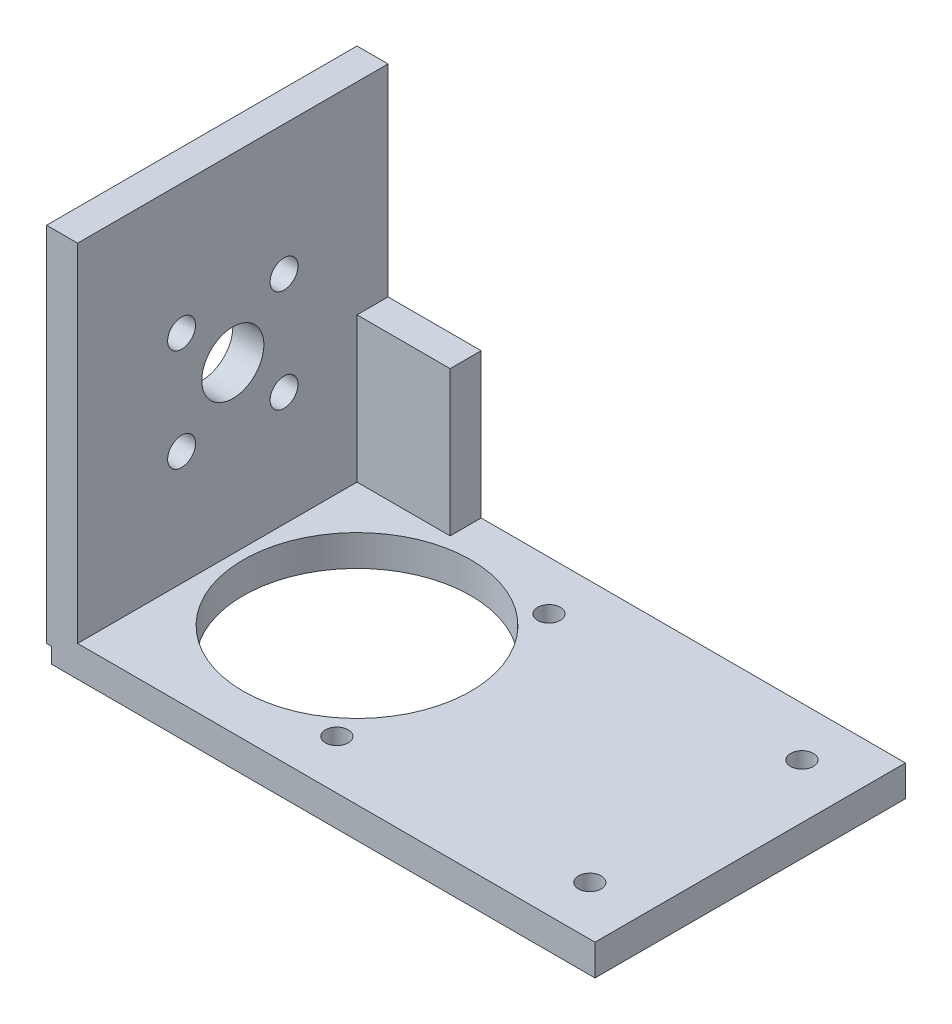
SolidWorks part; units mm, degrees
ref_plane "Front Plane" through (0, 0, 0) normal (0, 0, 1) x (1, 0, 0)
ref_plane "Top Plane" through (0, 0, 0) normal (0, 1, 0) x (1, 0, 0)
ref_plane "Right Plane" through (0, 0, 0) normal (1, 0, 0) x (0, 0, -1)
ref_plane "PZ_m15_000" through (0, 0, -15) normal (0, 0, 1) x (1, 0, 0)
sketch "S_box1" plane through (0, 0, -15) normal (0, 0, 1) x (1, 0, 0)
  line L0 (-15, -17.5) -> (-12, -17.5)
  line L1 (-12, -17.5) -> (-12, 17.5)
  line L2 (-12, 17.5) -> (-15, 17.5)
  line L3 (-15, 17.5) -> (-15, -17.5)
  dimension "P1" = 15
  dimension "P2" = 17.5
  dimension "P3" = 12
  dimension "P4" = 17.5
  dimension "P5" = 12
  dimension "P6" = 17.5
  dimension "P7" = 15
  dimension "P8" = 17.5
extrude "Boss_1" add sketch "S_box1" along normal blind 30
sketch "S_box2" plane through (0, 0, -15) normal (0, 0, 1) x (1, 0, 0)
  line L0 (-14.5, -19) -> (38, -19)
  line L1 (38, -19) -> (38, -16)
  line L2 (38, -16) -> (-14.5, -16)
  line L3 (-14.5, -16) -> (-14.5, -19)
  dimension "P1" = 14.5
  dimension "P2" = 19
  dimension "P3" = 38
  dimension "P4" = 19
  dimension "P5" = 38
  dimension "P6" = 16
  dimension "P7" = 14.5
  dimension "P8" = 16
extrude "Boss_2" add sketch "S_box2" along normal blind 30
sketch "S_box3" plane through (0, 0, -15) normal (0, 0, 1) x (1, 0, 0)
  line L0 (-14.5, -18.5) -> (-3, -18.5)
  line L1 (-3, -18.5) -> (-3, -2)
  line L2 (-3, -2) -> (-14.5, -2)
  line L3 (-14.5, -2) -> (-14.5, -18.5)
  dimension "P1" = 14.5
  dimension "P2" = 18.5
  dimension "P3" = 3
  dimension "P4" = 18.5
  dimension "P5" = 3
  dimension "P6" = 2
  dimension "P7" = 14.5
  dimension "P8" = 2
extrude "Boss_3" add sketch "S_box3" along normal blind 3
ref_plane "PX_m15_100" through (-15.1, 0, 0) normal (1, 0, 0) x (0, 0, -1)
sketch "S_hole4" plane through (-15.1, 0, 0) normal (1, 0, 0) x (0, 0, -1)
  circle A0 centre (0, 0) radius 3
  dimension "D1_S_hole4" = 6
extrude "Hole_4" cut sketch "S_hole4" along normal blind 3.2
sketch "S_hole5" plane through (-15.1, 0, 0) normal (1, 0, 0) x (0, 0, -1)
  circle A0 centre (-4.9497, 4.9497) radius 1.35
  dimension "D1_S_hole5" = 2.7
  dimension "P2" = 4.9497
  dimension "P3" = 4.9497
extrude "Hole_5" cut sketch "S_hole5" along normal blind 3.2
sketch "S_hole6" plane through (-15.1, 0, 0) normal (1, 0, 0) x (0, 0, -1)
  circle A0 centre (-4.9497, -4.9497) radius 1.35
  dimension "D1_S_hole6" = 2.7
  dimension "P2" = 4.9497
  dimension "P3" = 4.9497
extrude "Hole_6" cut sketch "S_hole6" along normal blind 3.2
sketch "S_hole7" plane through (-15.1, 0, 0) normal (1, 0, 0) x (0, 0, -1)
  circle A0 centre (4.9497, -4.9497) radius 1.35
  dimension "D1_S_hole7" = 2.7
  dimension "P2" = 4.9497
  dimension "P3" = 4.9497
extrude "Hole_7" cut sketch "S_hole7" along normal blind 3.2
sketch "S_hole8" plane through (-15.1, 0, 0) normal (1, 0, 0) x (0, 0, -1)
  circle A0 centre (4.9497, 4.9497) radius 1.35
  dimension "D1_S_hole8" = 2.7
  dimension "P2" = 4.9497
  dimension "P3" = 4.9497
extrude "Hole_8" cut sketch "S_hole8" along normal blind 3.2
ref_plane "PY_m19_100" through (0, -19.1, 0) normal (0, 1, 0) x (1, 0, 0)
sketch "S_hole9" plane through (0, -19.1, 0) normal (0, 1, 0) x (1, 0, 0)
  circle A0 centre (0, 0) radius 11
  dimension "D1_S_hole9" = 22
extrude "Hole_9" cut sketch "S_hole9" along normal blind 3.2
sketch "S_hole10" plane through (0, -19.1, 0) normal (0, 1, 0) x (1, 0, 0)
  circle A0 centre (8.3, 10.25) radius 1.1
  dimension "D1_S_hole10" = 2.2
  dimension "P2" = 8.3
  dimension "P3" = 10.25
extrude "Hole_10" cut sketch "S_hole10" along normal blind 3.2
sketch "S_hole11" plane through (0, -19.1, 0) normal (0, 1, 0) x (1, 0, 0)
  circle A0 centre (8.3, -10.25) radius 1.1
  dimension "D1_S_hole11" = 2.2
  dimension "P2" = 8.3
  dimension "P3" = 10.25
extrude "Hole_11" cut sketch "S_hole11" along normal blind 3.2
sketch "S_hole12" plane through (0, -19.1, 0) normal (0, 1, 0) x (1, 0, 0)
  circle A0 centre (32.75, 10.25) radius 1.1
  dimension "D1_S_hole12" = 2.2
  dimension "P2" = 32.75
  dimension "P3" = 10.25
extrude "Hole_12" cut sketch "S_hole12" along normal blind 3.2
sketch "S_hole13" plane through (0, -19.1, 0) normal (0, 1, 0) x (1, 0, 0)
  circle A0 centre (32.75, -10.25) radius 1.1
  dimension "D1_S_hole13" = 2.2
  dimension "P2" = 32.75
  dimension "P3" = 10.25
extrude "Hole_13" cut sketch "S_hole13" along normal blind 3.2
equation "\"plate_t\" = 3"
equation "\"clearance\" = 0.4"
